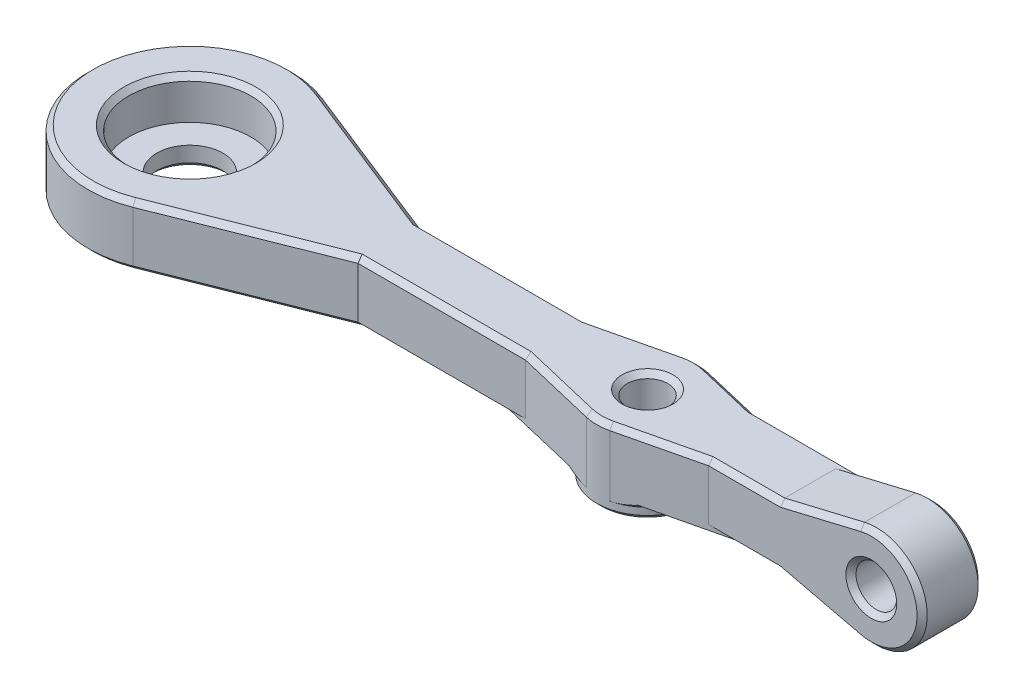
SolidWorks part; units mm, degrees
ref_plane "前视基准面" through (0, 0, 0) normal (0, 0, 1) x (1, 0, 0)
ref_plane "上视基准面" through (0, 0, 0) normal (0, 1, 0) x (1, 0, 0)
ref_plane "右视基准面" through (0, 0, 0) normal (1, 0, 0) x (0, 0, -1)
other "Configuration Table"
sketch "草图14" plane through (0, 0, 0) normal (0, 1, 0) x (1, 0, 0)
  line L0 (0, 0) -> (35, 0) construction
  line L1 (35, -1.5) -> (35, 1.5)
  line L2 (35, 1.5) -> (4.7697, 1.5)
  line L3 (35, -1.5) -> (4.7697, -1.5)
  arc A0 (4.7697, 1.5) -> (4.7697, -1.5) centre (0, 0) ccw
  point P6 (35, 0)
  dimension "D1" = 10
  dimension "D2" = 35
  dimension "D3" = 3
extrude "凸台-拉伸5" add sketch "草图14" along normal blind 3
sketch "草图15" plane through (0, 0, 0) normal (0, 1, 0) x (1, 0, 0)
  line L0 (0, 0) -> (22.5, 0) construction
  circle A0 centre (22.5, 0) radius 2.5
  dimension "D2" = 5
  dimension "D1" = 22.5
extrude "凸台-拉伸6" add sketch "草图15" along normal up to surface (3 mm away) up to face at (17.4424, 3, 0)
sketch "草图16" plane through (0, 0, 0) normal (0, 1, 0) x (1, 0, 0)
  circle A0 centre (0, 0) radius 1.625
  circle A1 centre (22.5, 0) radius 1
  dimension "D1" = 3.25
  dimension "D2" = 2
extrude "切除-拉伸9" cut sketch "草图16" along normal up to surface (3 mm away) up to face at (19.9712, 3, 0)
sketch "草图17" plane through (0, 0, 0) normal (0, 1, 0) x (1, 0, 0)
  circle A0 centre (0, 0) radius 3
  dimension "D1" = 6
extrude "切除-拉伸10" cut sketch "草图17" against normal blind 2 from surface at 3 starting at face at (0, 3, 1.625)
sketch "草图18" plane through (0, 0, 0) normal (0, 1, 0) x (1, 0, 0)
  line L0 (4.7697, -1.5) -> (20.5, -1.5) construction
  line L1 (20.5, 1.5) -> (4.7697, 1.5) construction
  line L2 (4.7697, -1.5) -> (9.7697, -1.5)
  line L3 (20.5, 1.5) -> (18, 1.5)
  line L4 (9.7697, 1.5) -> (1.8455, 4.647)
  line L5 (9.7697, -1.5) -> (1.8455, -4.647)
  line L6 (18, 1.5) -> (21.9219, 2.4322)
  line L7 (18, -1.5) -> (21.9219, -2.4322)
  line L8 (24.5, -1.5) -> (35, -1.5) construction
  line L9 (35, 1.5) -> (24.5, 1.5) construction
  line L10 (24.5, -1.5) -> (27, -1.5)
  line L11 (27, 1.5) -> (24.5, 1.5)
  line L12 (27, -1.5) -> (23.0781, -2.4322)
  line L13 (27, 1.5) -> (23.0781, 2.4322)
  line L14 (18, -1.5) -> (20.5, -1.5)
  line L15 (9.7697, 1.5) -> (4.7697, 1.5)
  arc A0 (24.5, 1.5) -> (20.5, 1.5) centre (22.5, 0) ccw construction
  arc A1 (20.5, -1.5) -> (24.5, -1.5) centre (22.5, 0) ccw construction
  arc A2 (4.7697, 1.5) -> (4.7697, -1.5) centre (0, 0) ccw construction
  arc A3 (24.5, 1.5) -> (23.0781, 2.4322) centre (22.5, 0) ccw
  arc A4 (20.5, -1.5) -> (21.9219, -2.4322) centre (22.5, 0) ccw
  arc A5 (4.7697, 1.5) -> (1.8455, 4.647) centre (0, 0) ccw
  arc A6 (21.9219, 2.4322) -> (20.5, 1.5) centre (22.5, 0) ccw
  arc A7 (23.0781, -2.4322) -> (24.5, -1.5) centre (22.5, 0) ccw
  arc A8 (1.8455, -4.647) -> (4.7697, -1.5) centre (0, 0) ccw
  dimension "D1" = 2.5
  dimension "D2" = 2.5
  dimension "D3" = 5
  dimension "D4" = 5
  dimension "D5" = 2.5
  dimension "D6" = 2.5
extrude "凸台-拉伸7" add sketch "草图18" along normal up to surface (3 mm away) up to face at (0, 3, 3)
sketch "草图19" plane through (0, 0, 0) normal (0, 0, 1) x (1, 0, 0)
  line L0 (35, 3) -> (35, 0) construction
  circle A0 centre (35, 1.5) radius 1 construction
  circle A1 centre (35, 1.5) radius 2.5
  dimension "D1" = 2
  dimension "D2" = 5
extrude "凸台-拉伸8" add sketch "草图19" along normal up to surface (3 mm away) from surface at -1.5 up to face at (31, 1.5, 1.5) starting at face at (31, 1.5, -1.5)
sketch "草图20" plane through (0, 0, 0) normal (0, 0, 1) x (1, 0, 0)
  circle A0 centre (35, 1.5) radius 1
  dimension "D1" = 2
extrude "切除-拉伸11" cut sketch "草图20" along normal up to surface (3 mm away) from surface at -1.5 up to face at (31.125, 1.5, 1.5) starting at face at (13.8848, 1.5, -1.5)
sketch "草图21" plane through (0, 0, 0) normal (0, 0, 1) x (1, 0, 0)
  line L0 (27, 3) -> (33, 3) construction
  line L1 (27, 0) -> (33, 0) construction
  line L2 (30.5, 3) -> (33, 3)
  line L3 (30.5, 0) -> (33, 0)
  line L4 (30.5, 3) -> (34.4219, 3.9322)
  line L5 (30.5, 0) -> (34.4219, -0.9322)
  arc A0 (33, 0) -> (33, 3) centre (35, 1.5) ccw construction
  arc A1 (33, 0) -> (34.4219, -0.9322) centre (35, 1.5) ccw
  arc A2 (34.4219, 3.9322) -> (33, 3) centre (35, 1.5) ccw
  dimension "D1" = 2.5
  dimension "D2" = 2.5
extrude "凸台-拉伸9" add sketch "草图21" along normal up to surface (3 mm away) from surface
chamfer "倒角2" distance 0.25 angle 45 27 edges at (28.75, 0, 1.5) (28.75, 3, 1.5) (25.0391, 3, 1.9661) (-5, 0, 0) (-5, 3, 0) (5.8076, 0, -3.0735) (5.8076, 3, -3.0735) (13.8848, 0, 1.5) (13.8848, 3, 1.5) (5.8076, 0, 3.0735) (5.8076, 3, 3.0735) (34, 1.5, 1.5) (36, 1.5, -1.5) (37.5, 1.5, 1.5) (32.4609, 3.4661, 1.5) (32.4609, 3.4661, -1.5) (37.5, 1.5, -1.5) (28.75, 0, -1.5) (32.4609, -0.4661, 1.5) (32.4609, -0.4661, -1.5) (22.5, 3, 1) (22.5, 3, -2.5) (25.0391, 3, -1.9661) (13.8848, 0, -1.5) (19.9609, 3, -1.9661) (22.5, 3, 2.5) (19.9609, 3, 1.9661)
sketch "草图22" plane through (0, 0, 0) normal (0, 1, 0) x (1, 0, 0)
  circle A0 centre (22.5, 0) radius 2.5
  circle A1 centre (22.5, 0) radius 1
  dimension "D1" = 5
  dimension "D2" = 2
extrude "凸台-拉伸10" add sketch "草图22" against normal blind 0.85
chamfer "倒角4" distance 0.25 angle 45 6 edges at (22.5, -0.85, 2.5) (20, 0, 0) (25, 0, 0) (22.5, -0.85, 1) (0, 3, 3) (0, 0, 1.625)
